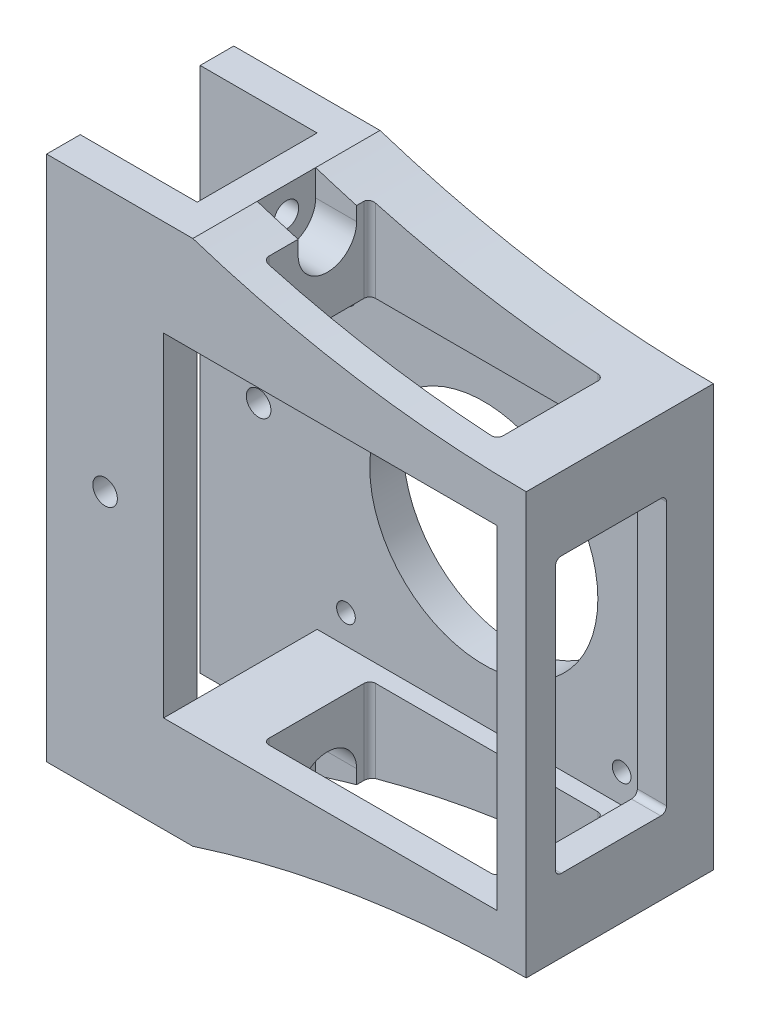
SolidWorks part; units mm, degrees
material "PBT Общее назначение"
ref_plane "Спереди" through (0, 0, 0) normal (0, 0, 1) x (1, 0, 0)
ref_plane "Сверху" through (0, 0, 0) normal (0, 1, 0) x (1, 0, 0)
ref_plane "Справа" through (0, 0, 0) normal (1, 0, 0) x (0, 0, -1)
sketch "Эскиз1" plane through (0, 0, 0) normal (0, 0, 1) x (1, 0, 0)
  line L0 (0, -45) -> (0, 45)
  line L1 (0, 45) -> (25, 45)
  line L2 (0, -45) -> (25, -45)
  line L3 (82, 36) -> (0, 36) construction
  line L4 (82, 36) -> (82, -36)
  line L5 (0, 0) -> (82, 0) construction
  arc A0 (25, 45) -> (82, 36) centre (82, 221) ccw
  arc A1 (25, -45) -> (82, -36) centre (82, -221) cw
  dimension "D1" = 45
  dimension "D2" = 82
  dimension "D3" = 25
  dimension "D4" = 36
  dimension "D5" = 57
extrude "Бобышка-Вытянуть1" add sketch "Эскиз1" along normal blind 52
sketch "Эскиз2" plane through (0, 0, 52) normal (0, 0, 1) x (1, 0, 0)
  line L0 (82, 0) -> (-10.2579, 0) construction
  line L1 (82, -36) -> (82, 36) construction
  line L2 (77, 28.5) -> (77, -28.5)
  line L3 (77, 28.5) -> (20, 28.5)
  line L4 (77, -28.5) -> (20, -28.5)
  line L5 (20, 28.5) -> (20, -28.5)
  line L6 (82, 0) -> (20, 0) construction
  line L7 (0, 45) -> (0, -45) construction
  dimension "D1" = 57
  dimension "D2" = 20
  dimension "D3" = 57
extrude "Вырез-Вытянуть1" cut sketch "Эскиз2" against normal through all
sketch "Эскиз3" plane through (0, 0, 0) normal (-1, 0, 0) x (0, 0, 1)
  line L0 (26, 45) -> (26, -45) construction
  line L1 (52, 45) -> (0, 45) construction
  line L2 (52, -45) -> (0, -45) construction
  line L3 (15.75, 45) -> (36.25, 45)
  line L4 (15.75, 45) -> (15.75, -45)
  line L5 (36.25, 45) -> (36.25, -45)
  line L6 (15.75, -45) -> (36.25, -45)
  line L7 (26, -45) -> (26, 45) construction
  dimension "D1" = 20.5
extrude "Вырез-Вытянуть2" cut sketch "Эскиз3" against normal blind 20
sketch "Эскиз4" plane through (0, 0, 0) normal (0, 0, -1) x (-1, 0, 0)
  line L4 (0, 45) -> (-25, 45)
  line L5 (-82, 36) -> (-82, -36)
  line L6 (-25, -45) -> (0, -45)
  line L7 (0, -45) -> (0, 45)
  line L8 (0, 45) -> (-25, 45)
  line L9 (-82, 36) -> (-82, -36)
  line L10 (-25, -45) -> (0, -45)
  line L11 (0, -45) -> (0, 45)
  arc A2 (-82, 36) -> (-25, 45) centre (-82, 221) ccw
  arc A3 (-25, -45) -> (-82, -36) centre (-82, -221) ccw
  arc A4 (-82, 36) -> (-25, 45) centre (-82, 221) ccw
  arc A5 (-25, -45) -> (-82, -36) centre (-82, -221) ccw
  dimension "D1" = 0
extrude "Вырез-Вытянуть3" cut sketch "Эскиз4" against normal blind 10
sketch "Эскиз5" plane through (0, 0, 52) normal (0, 0, 1) x (1, 0, 0)
  line L4 (25, 45) -> (0, 45)
  line L5 (0, 45) -> (0, -45)
  line L6 (0, -45) -> (25, -45)
  line L7 (82, -36) -> (82, 36)
  line L8 (25, 45) -> (0, 45)
  line L9 (0, 45) -> (0, -45)
  line L10 (0, -45) -> (25, -45)
  line L11 (82, -36) -> (82, 36)
  arc A2 (82, -36) -> (25, -45) centre (82, -221) ccw
  arc A3 (25, 45) -> (82, 36) centre (82, 221) ccw
  arc A4 (82, -36) -> (25, -45) centre (82, -221) ccw
  arc A5 (25, 45) -> (82, 36) centre (82, 221) ccw
  dimension "D1" = 0
extrude "Вырез-Вытянуть4" cut sketch "Эскиз5" against normal blind 10
sketch "Эскиз6" plane through (0, 0, 10) normal (0, 0, -1) x (-1, 0, 0)
  line L0 (-20, -28.5) -> (-77, -28.5) construction
  line L1 (-20, 28.5) -> (-20, -28.5) construction
  line L2 (-77, 28.5) -> (-20, 28.5) construction
  line L3 (-77, -28.5) -> (-77, 28.5) construction
  line L4 (-20, -28.5) -> (-77, -28.5)
  line L5 (-20, 28.5) -> (-20, -28.5)
  line L6 (-77, 28.5) -> (-20, 28.5)
  line L7 (-77, -28.5) -> (-77, 28.5)
extrude "Бобышка-Вытянуть2" add sketch "Эскиз6" against normal up to surface (5.75 mm away) up to face at (13.3333, 0, 15.75)
sketch "Эскиз7" plane through (0, 0, 15.75) normal (0, 0, 1) x (1, 0, 0)
  line L0 (20, -28.5) -> (20, 28.5) construction
  line L1 (77, -28.5) -> (20, -28.5) construction
  line L2 (77, 28.5) -> (77, -28.5) construction
  line L3 (20, 28.5) -> (77, 28.5) construction
  line L4 (20, -28.5) -> (20, 28.5) construction
  line L5 (77, -28.5) -> (20, -28.5) construction
  line L6 (77, 28.5) -> (77, -28.5) construction
  line L7 (20, 28.5) -> (77, 28.5) construction
  line L8 (48.5, -28.5) -> (48.5, 28.5) construction
  line L9 (20, 0) -> (77, 0) construction
  circle A0 centre (48.5, 0) radius 19.5
  dimension "D1" = 39
extrude "Вырез-Вытянуть5" cut sketch "Эскиз7" against normal through all
sketch "Эскиз8" plane through (20, 0, 0) normal (-1, 0, 0) x (0, 0, 1)
  line L0 (42, -36) -> (10, -36) construction
  line L1 (36.25, -36) -> (15.75, -36) construction
  line L2 (15.75, -45) -> (36.25, -45) construction
  line L3 (15.75, -45) -> (36.25, -45) construction
  line L4 (15.75, -28.5) -> (15.75, -45) construction
  line L5 (36.25, -45) -> (36.25, -28.5) construction
  line L6 (15.75, -36) -> (15.75, -45) construction
  line L7 (36.25, -45) -> (36.25, -36) construction
  line L8 (26, -45) -> (26, -36) construction
  line L9 (36.25, -40.5) -> (15.75, -40.5) construction
  line L10 (36.25, 45) -> (15.75, 45) construction
  line L12 (15.75, 45) -> (15.75, 28.5) construction
  line L13 (36.25, 28.5) -> (36.25, 45) construction
  line L14 (36.25, 45) -> (15.75, 45) construction
  line L15 (26, 36) -> (26, 45) construction
  line L16 (15.75, 45) -> (15.75, 36) construction
  line L17 (36.25, 36) -> (36.25, 45) construction
  line L18 (42, 36) -> (10, 36) construction
  line L19 (36.25, 36) -> (15.75, 36) construction
  line L20 (15.75, 40.5) -> (36.25, 40.5) construction
  circle A0 centre (26, -40.5) radius 2.1
  circle A1 centre (26, 40.5) radius 2.1
  dimension "D1" = 4.2
  dimension "D2" = 4.2
extrude "Вырез-Вытянуть6" cut sketch "Эскиз8" against normal through all
sketch "Эскиз9" plane through (0, 0, 10) normal (0, 0, -1) x (-1, 0, 0)
  line L0 (-82, 0) -> (0, 0) construction
  line L1 (-82, 36) -> (-82, -36) construction
  line L2 (0, -45) -> (0, 45) construction
ref_plane "СимY" through (0, 0, 0) normal (0, -1, 0) x (-1, 0, 0)
ref_plane "Плоскость2" through (25, 0, 0) normal (-1, 0, 0) x (0, 0, 1)
sketch "Эскиз10" plane through (25, 0, 0) normal (-1, 0, 0) x (0, 0, 1)
  circle A0 centre (26, 40.5) radius 2.1 construction
  circle A1 centre (26, -40.5) radius 2.1 construction
  circle A2 centre (26, 40.5) radius 2.1 construction
  circle A3 centre (26, -40.5) radius 2.1 construction
  circle A4 centre (26, 40.5) radius 5
  circle A5 centre (26, -40.5) radius 5
  dimension "D1" = 10
  dimension "D2" = 10
extrude "Вырез-Вытянуть7" cut sketch "Эскиз10" against normal through all
sketch "Эскиз12" plane through (0, 0, 10) normal (0, 0, -1) x (-1, 0, 0)
  line L0 (-20, 45) -> (0, 45) construction
  line L1 (0, 45) -> (0, -45) construction
  line L2 (-20, -45) -> (0, -45) construction
  line L3 (-20, 45) -> (0, 45) construction
  line L4 (0, 45) -> (0, -45) construction
  line L5 (-20, -45) -> (0, -45) construction
  line L6 (-20, 45) -> (-20, 28.5) construction
  line L7 (-20, 45) -> (-20, -45) construction
  line L8 (-20, 0) -> (0, 0) construction
  line L9 (-10, 45) -> (-10, -45) construction
  circle A0 centre (-10, 0) radius 2.1
  dimension "D1" = 4.2
extrude "Вырез-Вытянуть8" cut sketch "Эскиз12" against normal through all
sketch "Эскиз13" plane through (82, 0, 0) normal (1, 0, 0) x (0, 0, -1)
  line L0 (-42, 0) -> (-10, 0) construction
  line L1 (-42, -36) -> (-42, 36) construction
  line L2 (-26, 0) -> (-26, -36.6008) construction
  line L3 (-23.8206, -36) -> (-10, -36) construction
ref_plane "СимZ" through (0, 0, 26) normal (0, 0, 1) x (0, -1, 0)
sketch "Эскиз14" plane through (0, 0, 10) normal (0, 0, -1) x (-1, 0, 0)
  line L0 (-48.5, 0) -> (-48.5, 19.5) construction
  line L1 (-48.5, 0) -> (-29, 0) construction
  line L2 (-72.07, 23.57) -> (-24.93, 23.57) construction
  line L3 (-72.07, 23.57) -> (-72.07, -23.57) construction
  line L4 (-24.93, 23.57) -> (-24.93, -23.57) construction
  line L5 (-72.07, -23.57) -> (-24.93, -23.57) construction
  line L6 (-48.5, 23.57) -> (-48.5, -23.57) construction
  line L7 (-24.93, 0) -> (-72.07, 0) construction
  circle A0 centre (-48.5, 0) radius 19.5 construction
  circle A1 centre (-48.5, 0) radius 19.5 construction
  circle A2 centre (-72.07, 23.57) radius 1.6
  circle A3 centre (-24.93, 23.57) radius 1.6
  circle A4 centre (-24.93, -23.57) radius 1.6
  circle A5 centre (-72.07, -23.57) radius 1.6
  dimension "D3" = 3.2
  dimension "D4" = 3.2
  dimension "D5" = 3.2
  dimension "D6" = 3.2
  dimension "D1" = 47.14
  dimension "D2" = 47.14
extrude "Вырез-Вытянуть9" cut sketch "Эскиз14" against normal up to surface (5.75 mm away) up to face at (10, 2.1, 15.75)
sketch "Эскиз15" plane through (82, 0, 0) normal (1, 0, 0) x (0, 0, -1)
  line L0 (-37, 23.5) -> (-18, 23.5)
  line L1 (-37, 23.5) -> (-37, -23.5)
  line L2 (-18, 23.5) -> (-18, -23.5)
  line L3 (-37, -23.5) -> (-18, -23.5)
  line L5 (-42, -36) -> (-42, 36) construction
  line L6 (-10, 36) -> (-10, -36) construction
  line L7 (-15.75, -28.5) -> (-42, -28.5) construction
  line L8 (-15.75, -28.5) -> (-42, -28.5) construction
  line L9 (-15.75, 28.5) -> (-42, 28.5) construction
  line L10 (-15.75, 28.5) -> (-42, 28.5) construction
  dimension "D1" = 5
  dimension "D2" = 8
  dimension "D3" = 5
  dimension "D4" = 5
  dimension "D5" = 5
extrude "Вырез-Вытянуть10" cut sketch "Эскиз15" against normal up to surface (5 mm away) up to face at (77, 0, 28.875)
sketch "Sketch1" plane through (0, 28.5, 0) normal (0, -1, 0) x (1, 0, 0)
  line L0 (72, 37) -> (72, 18.75)
  line L1 (72, 37) -> (32, 37)
  line L2 (72, 18.75) -> (32, 18.75)
  line L3 (32, 37) -> (32, 18.75)
  line L4 (77, 15.75) -> (77, 42) construction
  line L5 (20, 42) -> (77, 42) construction
  line L6 (77, 15.75) -> (20, 15.75) construction
  dimension "D1" = 5
  dimension "D2" = 40
  dimension "D3" = 5
  dimension "D4" = 3
extrude "Cut-Extrude1" cut sketch "Sketch1" against normal through all and the other way through all
fillet "Скругление1" radius 1 4 edges at (79.5, -23.5, 18) (79.5, -23.5, 37) (79.5, 23.5, 37) (79.5, 23.5, 18)
fillet "Скругление2" radius 1 4 edges at (32, 35.6924, 18.75) (72, 32.3852, 18.75) (72, 32.3852, 37) (32, 35.6924, 37)
fillet "Скругление3" radius 1 4 edges at (72, -32.3852, 37) (32, -35.6924, 37) (32, -35.6924, 18.75) (72, -32.3852, 18.75)
sketch "Эскиз16" plane through (0, 0, 42) normal (0, 0, 1) x (1, 0, 0)
  line L0 (72, 36.2705) -> (72, 28.5) construction
  line L1 (72, 36.2705) -> (72, 28.5)
  line L2 (20, 28.5) -> (77, 28.5) construction
  line L3 (72, 28.5) -> (82, 28.5)
  line L4 (82, -36) -> (82, 36) construction
  line L5 (82, 28.5) -> (82, 36)
  arc A0 (25, 45) -> (82, 36) centre (82, 221) ccw construction
  arc A1 (72, 36.2705) -> (82, 36) centre (82, 221) ccw
extrude "Бобышка-Вытянуть3" add sketch "Эскиз16" against normal up to surface (32 mm away) up to face at (70.47, -23.57, 10)
sketch "Эскиз17" plane through (0, 0, 42) normal (0, 0, 1) x (1, 0, 0)
  line L0 (82, -36) -> (82, 36) construction
  line L1 (82, -36) -> (82, -28.5)
  line L2 (77, -28.5) -> (20, -28.5) construction
  line L3 (82, -28.5) -> (72, -28.5)
  line L4 (72, -28.5) -> (72, -36.2705) construction
  line L5 (72, -28.5) -> (72, -36.2705)
  arc A0 (82, -36) -> (25, -45) centre (82, -221) ccw construction
  arc A1 (82, -36) -> (72, -36.2705) centre (82, -221) ccw
extrude "Бобышка-Вытянуть4" add sketch "Эскиз17" against normal up to surface (32 mm away) up to face at (35.549, 0, 10)
sketch "Эскиз18" plane through (25, 0, 0) normal (1, 0, 0) x (0, 0, -1)
  line L0 (-31, 40.5) -> (-31, 45)
  line L1 (-42, 45) -> (-28.1794, 45) construction
  line L2 (-21, 40.5) -> (-21, 45)
  line L3 (-23.8206, 45) -> (-10, 45) construction
  line L4 (-31, 45) -> (-21, 45)
  arc A0 (-28.1794, 45) -> (-23.8206, 45) centre (-26, 40.5) ccw construction
  arc A1 (-31, 40.5) -> (-21, 40.5) centre (-26, 40.5) ccw
extrude "Вырез-Вытянуть11" cut sketch "Эскиз18" along normal up to surface (7 mm away) up to face at (32, 36.8591, 27.25)
sketch "Эскиз19" plane through (25, 0, 0) normal (1, 0, 0) x (0, 0, -1)
  line L0 (-31, -40.5) -> (-31, -45)
  line L1 (-42, -45) -> (-28.1794, -45) construction
  line L2 (-21, -40.5) -> (-21, -45)
  line L3 (-23.8206, -45) -> (-10, -45) construction
  line L4 (-31, -45) -> (-21, -45)
  arc A0 (-23.8206, -45) -> (-28.1794, -45) centre (-26, -40.5) ccw construction
  arc A1 (-21, -40.5) -> (-31, -40.5) centre (-26, -40.5) ccw
extrude "Вырез-Вытянуть12" cut sketch "Эскиз19" along normal up to surface (7 mm away) up to face at (32, -36.8591, 27.25)
